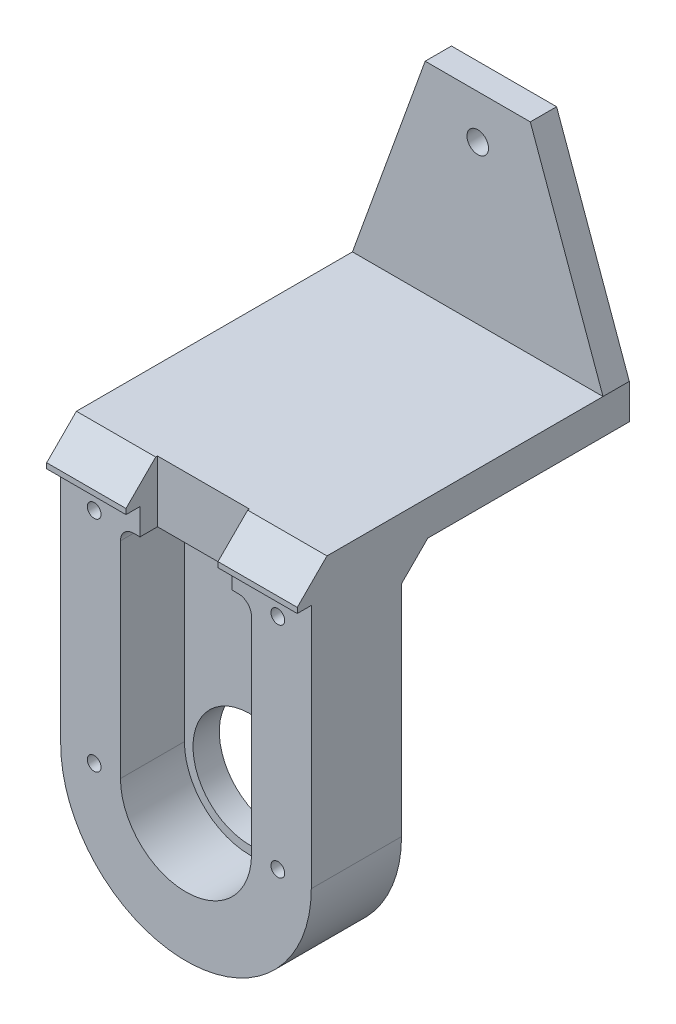
SolidWorks part; units mm, degrees
ref_plane "前视基准面" through (0, 0, 0) normal (0, 0, 1) x (1, 0, 0)
ref_plane "上视基准面" through (0, 0, 0) normal (0, 1, 0) x (1, 0, 0)
ref_plane "右视基准面" through (0, 0, 0) normal (1, 0, 0) x (0, 0, -1)
sketch "Model" plane through (0, 0, 0) normal (0, 0, 1) x (1, 0, 0)
  line L0 (-37.2121, 27.6698) -> (-8.6121, 27.6698)
  line L1 (-37.2121, 31.6698) -> (-8.6121, 31.6698)
  line L2 (-28.9121, 54.6698) -> (-37.2121, 31.6698)
  line L3 (-16.9121, 54.6698) -> (-8.6121, 31.6698)
  line L4 (-28.9121, 54.6698) -> (-16.9121, 54.6698)
  line L5 (-37.2121, 27.6698) -> (-8.6121, 27.6698)
  line L6 (-28.8921, 24.6698) -> (-16.9321, 24.6698)
  line L7 (-30.3921, -0.3302) -> (-30.3921, 23.1698)
  line L8 (-15.4321, -0.3302) -> (-15.4321, 23.1698)
  line L9 (-28.1621, 24.6698) -> (-28.1621, 27.6698)
  line L10 (-17.6621, 24.6698) -> (-17.6621, 27.6698)
  line L11 (-8.6121, 27.6698) -> (-8.6121, -0.3302)
  line L12 (-8.6121, 31.6698) -> (-8.6121, -0.3302)
  line L13 (-37.2121, 27.6698) -> (-37.2121, -0.3302)
  line L14 (-37.2121, 31.6698) -> (-37.2121, -0.3302)
  circle A0 centre (-22.9121, -0.3302) radius 6.5
  arc A1 (-15.4321, 23.1698) -> (-16.9321, 24.6698) centre (-16.9321, 23.1698) ccw
  arc A2 (-28.8921, 24.6698) -> (-30.3921, 23.1698) centre (-28.8921, 23.1698) ccw
  arc A3 (-37.2121, -0.3302) -> (-8.6121, -0.3302) centre (-22.9121, -0.3302) ccw
  arc A4 (-30.3921, -0.3302) -> (-15.4321, -0.3302) centre (-22.9121, -0.3302) ccw
  circle A5 centre (-12.4321, -0.3302) radius 0.7835
  circle A6 centre (-33.3921, -0.3302) radius 0.7835
  circle A7 centre (-12.4321, 24.6698) radius 0.7835
  circle A8 centre (-33.3921, 24.6698) radius 0.7835
  circle A9 centre (-33.2121, 29.6698) radius 1.2294
  circle A10 centre (-22.9121, 29.6698) radius 1.2294
  circle A11 centre (-12.6121, 29.6698) radius 1.2294
  circle A12 centre (-22.9121, 49.6698) radius 1.2294
extrude "凸台-拉伸1" add sketch "Model" along normal blind 10.3 contours A4 L7 A2 L6 L9 L0 L13 A3 L11 L10 A1 L8 A8 A7 A6 A5 | L1 L14 L0 L5 L12 A11 A10 A9 | A9 | A10 | A11 region at (-36.9233, 29.6698, 0) region at (-32.6871, 27.1592, 0) region at (-33.2121, 29.6698, 0) region at (-22.9121, 29.6698, 0) region at (-12.6121, 29.6698, 0)
extrude "凸台-拉伸2" add sketch "Model<3>" along normal blind 8.3 contours L6 L10 L5 L9 region at (-22.9121, 26.1698, 0)
sketch "Model<3>" plane through (0, 0, 0) normal (0, 0, 1) x (1, 0, 0) same geometry as "Model"
extrude "凸台-拉伸3" add sketch "Model<4>" along normal blind 3 contours L7 A4 L8 A1 L6 A2 A0 region at (-22.9121, 12.9919, 0)
sketch "Model<4>" plane through (0, 0, 0) normal (0, 0, 1) x (1, 0, 0) same geometry as "Model"
sketch "草图2" plane through (0, 0, 10.3) normal (0, 0, 1) x (1, 0, 0)
  line L0 (-37.2121, 27.6698) -> (-8.6121, 27.6698) construction
  line L1 (-37.2121, 27.6698) -> (-8.6121, 27.6698)
  line L2 (-37.2121, 27.6698) -> (-37.2121, 31.6698)
  line L3 (-37.2121, 31.6698) -> (-8.6121, 31.6698)
  line L4 (-8.6121, 31.6698) -> (-8.6121, 27.6698)
extrude "凸台-拉伸4" add sketch "草图2" along normal blind 1.6
sketch "草图3" plane through (0, 27.6698, 0) normal (0, -1, 0) x (1, 0, 0)
  line L0 (-17.6621, 10.3) -> (-17.6621, 8.3) construction
  line L1 (-28.1621, 10.3) -> (-28.1621, 8.3) construction
  line L2 (-28.1621, 8.3) -> (-17.6621, 8.3) construction
  line L3 (-17.6621, 13.389) -> (-17.6621, 8.3)
  line L4 (-28.1621, 13.389) -> (-28.1621, 8.3)
  line L5 (-28.1621, 8.3) -> (-17.6621, 8.3)
  line L6 (-28.1621, 13.389) -> (-17.6621, 13.389)
extrude "切除-拉伸1" cut sketch "草图3" against normal blind 5.6
extrude "凸台-拉伸5" add sketch "Model<5>" against normal blind 26 contours L1 L14 L0 L5 L12 A11 A10 A9 | A11 | A10 | A9 region at (-36.9233, 29.6698, 0) region at (-33.2121, 29.6698, 0) region at (-22.9121, 29.6698, 0) region at (-12.6121, 29.6698, 0)
sketch "Model<5>" plane through (0, 0, 0) normal (0, 0, 1) x (1, 0, 0) same geometry as "Model"
extrude "凸台-拉伸6" add sketch "Model<6>" along normal blind 3 contours A7 | A8 | A6 | A5 region at (-12.4321, -0.3302, 0) region at (-33.3921, -0.3302, 0) region at (-12.4321, 24.6698, 0) region at (-33.3921, 24.6698, 0)
sketch "Model<6>" plane through (0, 0, 0) normal (0, 0, 1) x (1, 0, 0) same geometry as "Model"
sketch "草图4" plane through (0, 0, -26) normal (0, 0, -1) x (-1, 0, 0)
  line L0 (28.9121, 54.6698) -> (37.2121, 31.6698) construction
  line L1 (28.9121, 54.6698) -> (16.9121, 54.6698) construction
  line L2 (16.9121, 54.6698) -> (8.6121, 31.6698) construction
  line L3 (28.9121, 54.6698) -> (37.2121, 31.6698)
  line L4 (28.9121, 54.6698) -> (16.9121, 54.6698)
  line L5 (16.9121, 54.6698) -> (8.6121, 31.6698)
  line L10 (37.2121, 31.6698) -> (8.6121, 31.6698)
  line L11 (8.6121, 31.6698) -> (8.6121, 27.6698)
  line L12 (8.6121, 27.6698) -> (37.2121, 27.6698)
  line L13 (37.2121, 27.6698) -> (37.2121, 31.6698)
  line L14 (37.2121, 31.6698) -> (8.6121, 31.6698)
  line L15 (8.6121, 31.6698) -> (8.6121, 27.6698)
  line L16 (8.6121, 27.6698) -> (37.2121, 27.6698)
  line L17 (37.2121, 27.6698) -> (37.2121, 31.6698)
  circle A0 centre (22.9121, 49.6698) radius 1.2294 construction
  circle A1 centre (12.6121, 29.6698) radius 1.2294 construction
  circle A2 centre (33.2121, 29.6698) radius 1.2294 construction
  circle A3 centre (22.9121, 29.6698) radius 1.2294 construction
  circle A4 centre (22.9121, 49.6698) radius 1.2294
  circle A5 centre (12.6121, 29.6698) radius 1.2294
  circle A6 centre (33.2121, 29.6698) radius 1.2294
  circle A7 centre (22.9121, 29.6698) radius 1.2294
  line M5 (37.2121, 31.6698) -> (8.6121, 31.6698)
  dimension "D1" = 0
extrude "凸台-拉伸7" add sketch "草图4" against normal blind 3 contours L4 L5 L3 A4 M5 region at (-22.9121, 41.5196, -26)
extrude "切除-拉伸2" cut sketch "草图4<3>" against normal blind 8 contours A5 | A7 | A6 region at (-12.6121, 29.6698, -26) region at (-33.2121, 29.6698, -26) region at (-22.9121, 29.6698, -26)
sketch "草图4<3>" plane through (0, 0, -26) normal (0, 0, -1) x (-1, 0, 0) same geometry as "草图4"
chamfer "倒角1" distance 3 angle 45 1 edges at (-22.9121, 27.6698, 0)
sketch "草图5" plane through (-8.6121, 0, 0) normal (1, 0, 0) x (0, 0, -1)
  line L0 (-11.9, 27.6698) -> (-11.9, 28.2786)
  line L1 (-11.9, 27.6698) -> (-11.9, 31.6698) construction
  line L2 (-11.9, 28.2786) -> (-8.5087, 31.6698)
  line L3 (-11.9, 31.6698) -> (23, 31.6698) construction
  line L4 (-8.5087, 31.6698) -> (-12.98, 32.2865)
  line L5 (-12.98, 32.2865) -> (-11.9, 28.2786)
  line M7 (23, 31.6698) -> (-11.9, 31.6698)
  line M8 (-11.9, 31.6698) -> (-11.9, 27.6698)
  dimension "D1" = 45
extrude "切除-拉伸3" cut sketch "草图5" against normal blind 30 contours L2 M8 M7 region at (-8.6121, 30.5394, 10.7696)
